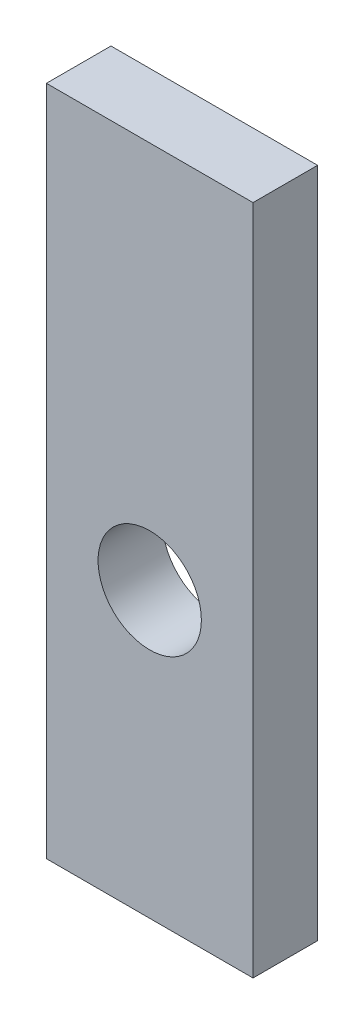
SolidWorks part; units mm, degrees
material "AISI 1020"
ref_plane "Plano frontal" through (0, 0, 0) normal (0, 0, 1) x (1, 0, 0)
ref_plane "Plano superior" through (0, 0, 0) normal (0, 1, 0) x (1, 0, 0)
ref_plane "Plano direito" through (0, 0, 0) normal (1, 0, 0) x (0, 0, -1)
sketch "Esboço1" plane through (0, 0, 0) normal (0, 0, 1) x (1, 0, 0)
  line L0 (-8, -22) -> (-8, 30)
  line L1 (-8, -22) -> (8, -22)
  line L2 (0, -22) -> (0, 30) construction
  line L3 (-8, 30) -> (8, 30)
  line L4 (8, -22) -> (8, 30)
  circle A0 centre (0, 0) radius 4
  dimension "D1" = 8
  dimension "D2" = 16
  dimension "D3" = 22
  dimension "D4" = 30
extrude "Extrusão1" add sketch "Esboço1" along normal mid plane 5
ref_plane "Plano1" through (0, 25, 0) normal (0, 1, 0) x (-1, 0, 0)
sketch "Esboço2" plane through (0, 25, 0) normal (0, 1, 0) x (-1, 0, 0)
  line L0 (0, -4.2229) -> (0, 4.8011) construction
ref_axis "Eixo1" through (0, 25, 4.8011) along (0, 0, -1)
